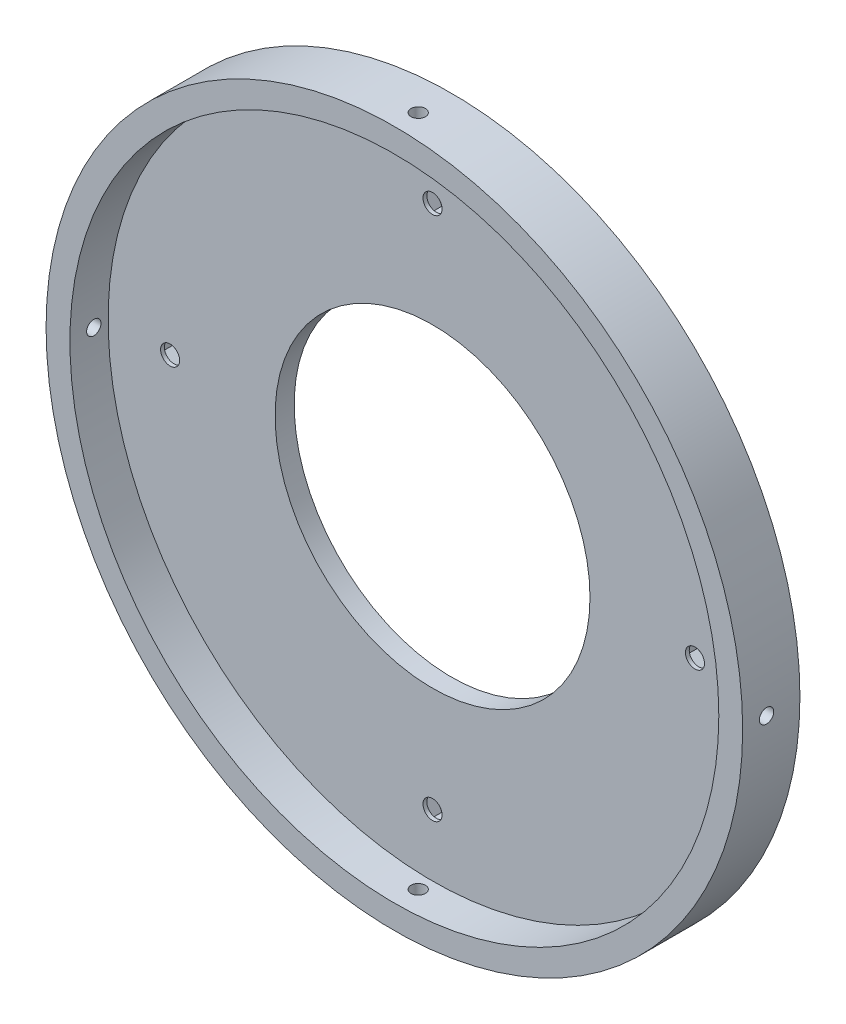
SolidWorks part; units mm, degrees
material "PET"
ref_plane "Front Plane" through (0, 0, 0) normal (0, 0, 1) x (1, 0, 0)
ref_plane "Top Plane" through (0, 0, 0) normal (0, 1, 0) x (1, 0, 0)
ref_plane "Right Plane" through (0, 0, 0) normal (1, 0, 0) x (0, 0, -1)
sketch "Sketch1" plane through (0, 0, 0) normal (0, 0, 1) x (1, 0, 0)
  circle A0 centre (0, 0) radius 73
  circle A1 centre (0, 0) radius 33
  dimension "D1" = 146
  dimension "D2" = 40
extrude "Boss-Extrude1" add sketch "Sketch1" along normal blind 4
sketch "Sketch2" plane through (0, 0, 4) normal (0, 0, 1) x (1, 0, 0)
  circle A0 centre (0, 0) radius 68
  circle A1 centre (0, 0) radius 73
  circle A2 centre (0, 0) radius 73
  dimension "D1" = 0
  dimension "D2" = 5
extrude "Boss-Extrude2" add sketch "Sketch2" along normal blind 8
sketch "Sketch3" plane through (0, 0, 0) normal (0, 1, 0) x (1, 0, 0)
  line L0 (-73, -12) -> (73, -12) construction
  circle A0 centre (0, -7) radius 1.5
  dimension "D2" = 3
  dimension "D1" = 5
extrude "Cut-Extrude1" cut sketch "Sketch3" against normal up to surface (73 mm away) up to face at (73, 0, 0)
pattern_circular "CirPattern1" count 4 over 360 about axis through (0, 0, 4) along (0, 0, -1) of "Cut-Extrude1"
sketch "Sketch9" plane through (0, 0, 0) normal (0, 0, -1) x (-1, 0, 0)
  point P0 (0, 55)
  point P4 (55, 0)
  point P6 (0, -55)
  point P8 (-55, 0)
  dimension "D1" = 55
  dimension "D2" = 0
  dimension "D3" = 55
  dimension "D4" = 55
  dimension "D5" = 55
hole_wizard "Ø4.0mm Dowel Hole1" positions "Sketch9" profile "Sketch10" hole size "Ø4.0" standard "ISO" end condition through all
sketch "Sketch10" plane through (0, 55, 0) normal (1, 0, 0) x (0, 1, 0)
  line L0 (0, 0) -> (0, 12)
  line L1 (0, 12) -> (2, 12)
  line L2 (2, 12) -> (2, 0)
  line L5 (2, 0) -> (0, 0)
  line L11 (0, -6.35) -> (0, 107.95) construction
  dimension "Thru Hole Dia." = 4
  dimension "Thru Hole Depth" = 12
sketch "Sketch13" plane through (0, 0, 0) normal (0, 0, -1) x (-1, 0, 0)
  line L0 (0, 0) -> (55, 0) construction
  line L1 (4.0415, 55) -> (2.0207, 58.5)
  line L2 (2.0207, 58.5) -> (-2.0207, 58.5)
  line L3 (-2.0207, 58.5) -> (-4.0415, 55)
  line L4 (-4.0415, 55) -> (-2.0207, 51.5)
  line L5 (-2.0207, 51.5) -> (2.0207, 51.5)
  line L6 (2.0207, 51.5) -> (4.0415, 55)
  line L7 (55, -4.0415) -> (58.5, -2.0207)
  line L8 (58.5, -2.0207) -> (58.5, 2.0207)
  line L9 (58.5, 2.0207) -> (55, 4.0415)
  line L10 (55, 4.0415) -> (51.5, 2.0207)
  line L11 (51.5, 2.0207) -> (51.5, -2.0207)
  line L12 (51.5, -2.0207) -> (55, -4.0415)
  line L13 (-4.0415, -55) -> (-2.0207, -58.5)
  line L14 (-2.0207, -58.5) -> (2.0207, -58.5)
  line L15 (2.0207, -58.5) -> (4.0415, -55)
  line L16 (4.0415, -55) -> (2.0207, -51.5)
  line L17 (2.0207, -51.5) -> (-2.0207, -51.5)
  line L18 (-2.0207, -51.5) -> (-4.0415, -55)
  line L19 (-55, 4.0415) -> (-58.5, 2.0207)
  line L20 (-58.5, 2.0207) -> (-58.5, -2.0207)
  line L21 (-58.5, -2.0207) -> (-55, -4.0415)
  line L22 (-55, -4.0415) -> (-51.5, -2.0207)
  line L23 (-51.5, -2.0207) -> (-51.5, 2.0207)
  line L24 (-51.5, 2.0207) -> (-55, 4.0415)
  circle A0 centre (0, 55) radius 3.5 construction
  circle A1 centre (55, 0) radius 3.5 construction
  circle A2 centre (0, -55) radius 3.5 construction
  circle A3 centre (-55, 0) radius 3.5 construction
  point P40 (0, 0)
  dimension "D1" = 7
extrude "Cut-Extrude2" cut sketch "Sketch13" against normal blind 3.2
